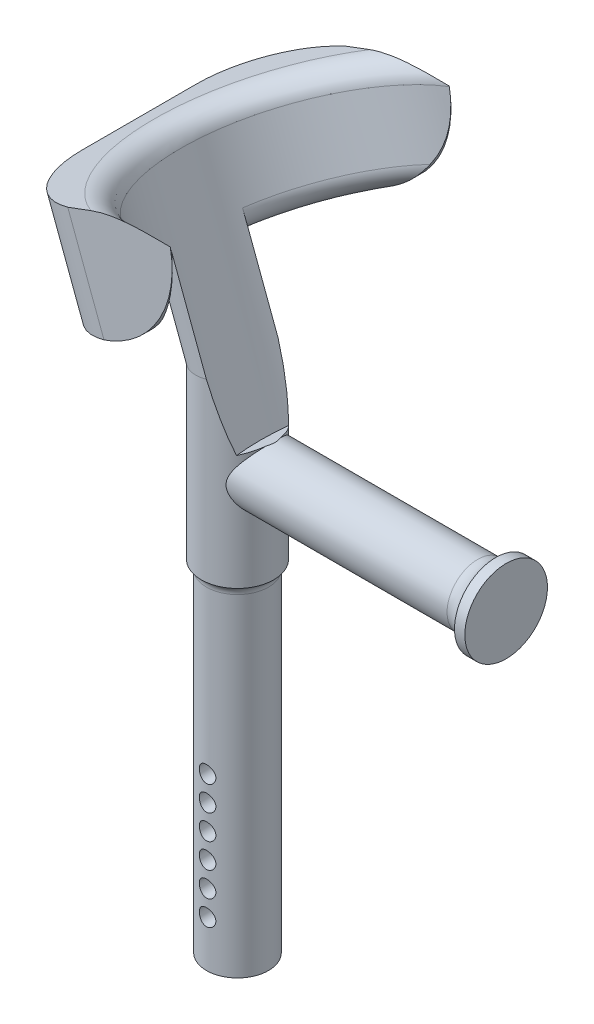
SolidWorks part; units mm, degrees
ref_plane "Plano frontal" through (0, 0, 0) normal (0, 0, 1) x (1, 0, 0)
ref_plane "Plano superior" through (0, 0, 0) normal (0, 1, 0) x (1, 0, 0)
ref_plane "Plano direito" through (0, 0, 0) normal (1, 0, 0) x (0, 0, -1)
sketch "Esboço1" plane through (0, 0, 0) normal (0, 1, 0) x (1, 0, 0)
  circle A0 centre (0, 0) radius 15
  dimension "D1" = 30
extrude "Ressalto-extrusão1" add sketch "Esboço1" along normal blind 150 and the other way blind 15 contours A0
sketch "Esboço2" plane through (0, 0, 0) normal (0, 0, 1) x (1, 0, 0)
  line L0 (0, 150) -> (0, -9.6485) construction
  line L1 (15, 150) -> (-15, 150) construction
  circle A0 centre (0, 7.3939) radius 3.9998
  circle A1 centre (0, 19.3939) radius 3.9998
  circle A2 centre (0, 31.3939) radius 3.9998
  circle A3 centre (0, 43.3939) radius 3.9998
  circle A4 centre (0, 55.3939) radius 3.9998
  circle A5 centre (0, 67.3939) radius 3.9998
  dimension "D1" = 12
  dimension "D2" = 12
  dimension "D3" = 12
  dimension "D4" = 12
  dimension "D5" = 12
extrude "Corte-extrusão1" cut sketch "Esboço2" against normal through all both and the other way through all
sketch "Esboço3" plane through (0, 150, 0) normal (0, 1, 0) x (1, 0, 0)
sketch "Esboço4" plane through (0, 150, 0) normal (0, 1, 0) x (1, 0, 0)
  circle A0 centre (0, 0) radius 17.5
  dimension "D1" = 35
extrude "Ressalto-extrusão2" add sketch "Esboço4" along normal blind 20
sketch "Esboço9" plane through (0, 170, 0) normal (0, 1, 0) x (1, 0, 0)
  circle A0 centre (0, 0) radius 17.5
sketch "Esboço10" plane through (0, 0, 0) normal (0, 0, 1) x (1, 0, 0)
  line L0 (0, 170) -> (0, 178.154)
  line L1 (17.5, 170) -> (-17.5, 170) construction
  line L2 (15, 193.154) -> (123.2199, 193.154)
  arc A0 (0, 178.154) -> (15, 193.154) centre (15, 178.154) cw
  dimension "D1" = 15
sketch "Esboço11" plane through (0, 0, 0) normal (1, 0, 0) x (0, 0, -1)
  circle A0 centre (0, 193.154) radius 14.8294
extrude "Ressalto-extrusão3" add sketch "Esboço11" along normal blind 125 separate body
extrude "Ressalto-extrusão4" add sketch "Esboço9" along normal blind 49.701
sketch "Esboço12" plane through (125, 0, 0) normal (1, 0, 0) x (0, 0, -1)
  circle A0 centre (0, 193.154) radius 20
  dimension "D1" = 40
extrude "Ressalto-extrusão5" add sketch "Esboço12" along normal blind 5
fillet "Filete2" radius 10 1 edges at (125, 193.154, -14.8294)
sketch "Esboço15" plane through (0, 219.701, 0) normal (0, 1, 0) x (1, 0, 0)
  circle A0 centre (0, 0) radius 17.5
sketch "Esboço16" plane through (0, 0, 0) normal (0, 0, 1) x (1, 0, 0)
  line L0 (0, 219.701) -> (0, 234.701)
  line L1 (17.5, 219.701) -> (-17.5, 219.701) construction
  line L2 (0, 234.701) -> (-13.5258, 270.8415)
  point P7 (-21.7281, 284.3488)
  point P12 (-45.0153, 234.701)
  point P13 (-18.687, 304.701)
  dimension "D1" = 15
sweep "Varredura2" add path "Esboço16" circular profile diameter 35 parameters "D3"=35
sketch "Esboço138" plane through (-90.5722, 242.0064, 0) normal (-0.3505, 0.9366, 0) x (0.9366, 0.3505, 0)
  line L0 (64.7655, -27.5) -> (64.7655, 27.5)
  line L1 (64.7655, 0) -> (118.871, 0) construction
  line L2 (99.7655, -67.4674) -> (99.7655, 67.4674)
  circle A0 centre (82.2655, 0) radius 17.5 construction
  circle A1 centre (82.2655, 0) radius 17.5 construction
  arc A4 (64.7655, 27.5) -> (99.7655, 67.4674) centre (105.0854, 27.5) cw
  arc A5 (64.7655, -27.5) -> (99.7655, -67.4674) centre (105.0854, -27.5) ccw
  point P6 (99.7655, 0)
  dimension "D1" = 27.5
extrude "Ressalto-extrusão6" add sketch "Esboço138" along normal blind 50
sketch "Esboço148" plane through (93.4362, 34.969, 0) normal (0.9366, 0.3505, 0) x (0, 0, -1)
  line L0 (-67.4674, 258.3998) -> (-67.4674, 308.3998)
  line L1 (-67.4674, 308.3998) -> (67.4674, 308.3998)
  line L2 (67.4674, 308.3998) -> (67.4674, 258.3998)
  line L3 (67.4674, 258.3998) -> (-67.4674, 258.3998)
extrude "Ressalto-extrusão7" add sketch "Esboço148" along normal blind 50
sketch "Esboço149" plane through (-108.0978, 288.8343, 0) normal (-0.3505, 0.9366, 0) x (0.9366, 0.3505, 0)
  line L0 (149.7655, 67.4674) -> (149.7655, -67.4674)
  line L1 (64.7655, 27.5) -> (64.7655, -27.5) construction
  arc A0 (149.7655, -67.4674) -> (149.7655, 67.4674) centre (149.7655, 0) cw
  dimension "D1" = 85
extrude "Corte-extrusão16" cut sketch "Esboço149" against normal blind 120
sketch "Esboço150" plane through (0, 0, 0) normal (0, 0, 1) x (1, 0, 0)
  line L0 (32.1663, 341.3289) -> (49.6919, 294.501)
  line L1 (49.6919, 294.501) -> (26.278, 285.7382)
  line L2 (49.6919, 294.501) -> (2.864, 276.9754) construction
  line L3 (26.278, 285.7382) -> (2.864, 276.9754)
  arc A0 (32.1663, 341.3289) -> (2.864, 276.9754) centre (-12.5549, 322.8441) cw
extrude "Corte-extrusão17" cut sketch "Esboço150" against normal through all both and the other way through all contours L0 A0 L3 L1 region at (35.8226, 300.8162, 0)
fillet "Filete10" radius 10 1 edges at (-31.0208, 317.6808, 0)
fillet "Filete12" radius 10 2 edges at (-4.7336, 274.132, -34.2756) (-4.7336, 274.132, 34.2756)
sketch "Esboço152" plane through (0, 0, 0) normal (1, 0, 0) x (0, 0, -1)
sketch "Esboço168" plane through (0, 0, 0) normal (0, 0, 1) x (1, 0, 0)
  line L0 (35.3832, 178.3246) -> (115.3832, 178.3246)
  line L1 (17.5, 178.3246) -> (116.2434, 178.3246) construction
  line L2 (50.3832, 178.3246) -> (35.3832, 178.3246)
  line L3 (52.3832, 178.3246) -> (67.3975, 178.3084)
  line L4 (69.3832, 178.318) -> (84.3832, 178.318)
  line L5 (86.3832, 178.318) -> (101.3832, 178.318)
  line L6 (50.3832, 178.3246) -> (52.3832, 178.3246)
  line L7 (67.3975, 178.3084) -> (69.3832, 178.318)
  line L8 (84.3832, 178.318) -> (86.3832, 178.318)
  line L9 (101.3832, 178.318) -> (103.3832, 178.318)
  arc A0 (35.3832, 178.3246) -> (50.3832, 178.3246) centre (42.8832, 171.7102) cw
  arc A1 (52.3832, 178.3246) -> (50.3832, 178.3246) centre (51.3832, 179.7805) cw
  arc A2 (52.3832, 178.3246) -> (67.3975, 178.3084) centre (59.8832, 171.7037) cw
  arc A3 (69.3832, 178.318) -> (67.3975, 178.3084) centre (68.3832, 179.7805) cw
  arc A4 (69.3832, 178.318) -> (84.3832, 178.318) centre (76.8832, 171.7037) cw
  arc A5 (86.3832, 178.318) -> (84.3832, 178.318) centre (85.3832, 179.7805) cw
  arc A6 (86.3832, 178.318) -> (101.3832, 178.318) centre (93.8832, 171.7037) cw
  arc A7 (103.3832, 178.318) -> (101.3832, 178.318) centre (102.3832, 179.7805) cw
  dimension "D2" = 10
  dimension "D3" = 2
  dimension "D1" = 80
  dimension "D4" = 15
sketch "Esboço169" plane through (0, 0, 0) normal (0, 0, 1) x (1, 0, 0)
extrude "Corte-extrusão19" cut sketch "Esboço168" against normal mid plane 30 contours A2 L0 | A4 L0 | A6 L0 | A0 L0 region at (42.8832, 179.7007, 0) region at (59.8832, 179.6997, 0) region at (76.8832, 179.6979, 0) region at (93.8832, 179.6979, 0)
fillet "Filete13" radius 5 1 edges at (0, 150, 15)
